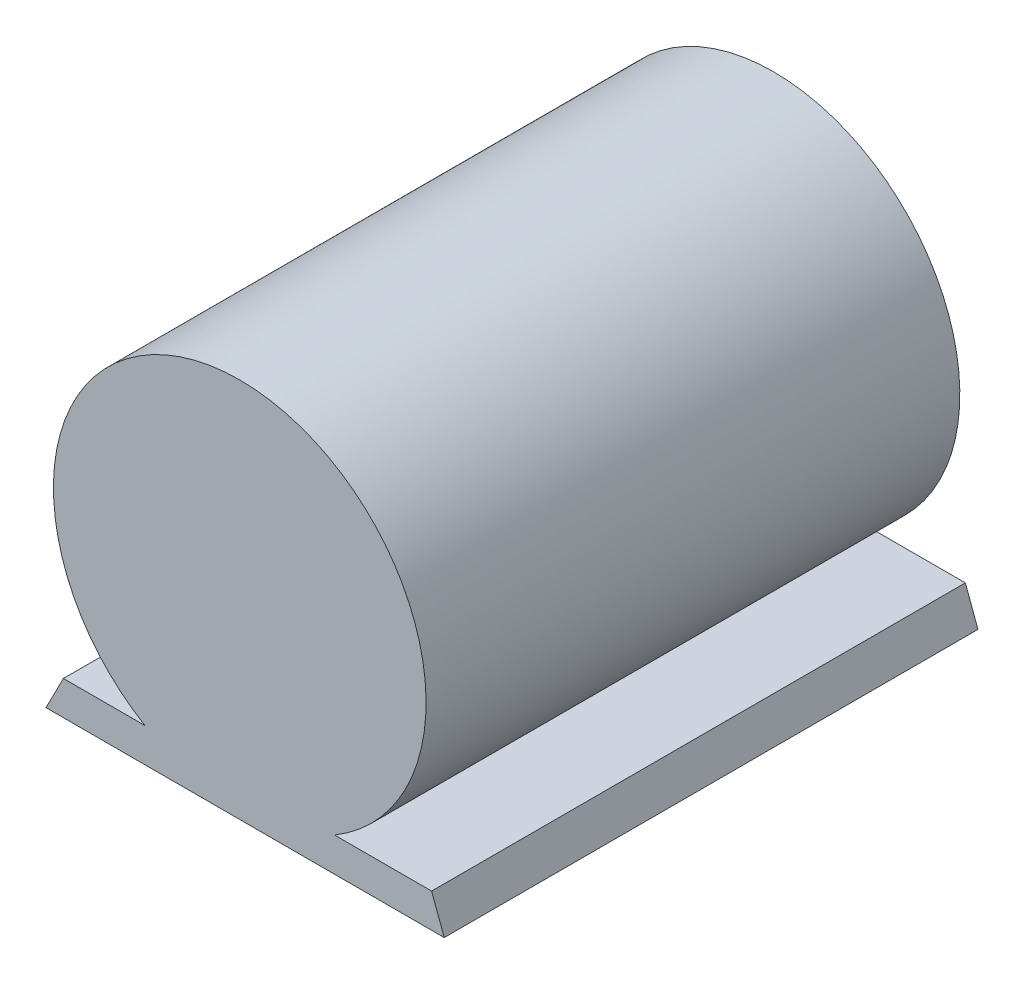
SolidWorks part; units mm, degrees
ref_plane "前视基准面" through (0, 0, 0) normal (0, 0, 1) x (1, 0, 0)
ref_plane "上视基准面" through (0, 0, 0) normal (0, 1, 0) x (1, 0, 0)
ref_plane "右视基准面" through (0, 0, 0) normal (1, 0, 0) x (0, 0, -1)
sketch "草图4" plane through (0, 0, 0) normal (0, 0, 1) x (1, 0, 0)
  line L0 (-63.4448, -57.7095) -> (-34.0779, -57.7095)
  line L1 (69.007, -57.7095) -> (73.5547, -69.9314)
  line L2 (73.5547, -69.9314) -> (-69.6979, -69.9314)
  line L3 (-69.6979, -69.9314) -> (-63.4448, -57.7095)
  line L4 (34.0779, -57.7095) -> (69.007, -57.7095)
  arc A0 (34.0779, -57.7095) -> (-34.0779, -57.7095) centre (0, 0) ccw
extrude "凸台-拉伸2" add sketch "草图4" along normal blind 192 contours L0 A0 | A0 L0 L3 L2 L1 region at (0.2576, -5.2892, 0)
sketch "草图5" plane through (0, 0, 0) normal (0, 0, -1) x (-1, 0, 0)
  circle A0 centre (0, 0) radius 60
extrude "切除-拉伸2" cut sketch "草图5" against normal blind 167
sketch "草图6" plane through (0, 0, 0) normal (0, 0, -1) x (-1, 0, 0)
  circle A0 centre (0, 0) radius 65
extrude "切除-拉伸3" cut sketch "草图6" against normal blind 167
sketch "草图7" plane through (0, 0, 0) normal (0, 0, -1) x (-1, 0, 0)
  line L0 (-50.4249, -41.0162) -> (50.4249, -41.0162)
  arc A0 (-50.4249, -41.0162) -> (50.4249, -41.0162) centre (0, 0) ccw
  arc A1 (-47.8977, -41.0162) -> (47.8977, -41.0162) centre (0, 0) ccw
  circle M1 centre (0, 0) radius 65
extrude "凸台-拉伸3" add sketch "草图7" against normal blind 81 contours A1 L0 M1 region at (49.1613, -42.0529, 0)
sketch "草图8" plane through (0, 0, 0) normal (0, 0, -1) x (-1, 0, 0)
  line L1 (-15.7468, -63.5922) -> (15.9641, -63.5922)
  line L2 (-15.7468, -63.5922) -> (-15.7468, -67.3976)
  line L3 (-15.7468, -67.3976) -> (15.9641, -67.3976)
  line L4 (15.9641, -63.5922) -> (15.9641, -67.3976)
extrude "凸台-拉伸4" add sketch "草图8" along normal blind 7
sketch "草图9" plane through (0, 0, -7) normal (0, 0, -1) x (-1, 0, 0)
  line L1 (-4.8769, -66.7917) -> (4.8769, -66.7917)
  line L2 (-4.8769, -66.7917) -> (-4.8769, -64.8313)
  line L3 (-4.8769, -64.8313) -> (4.8769, -64.8313)
  line L4 (4.8769, -66.7917) -> (4.8769, -64.8313)
  line L5 (-4.8769, -66.7917) -> (4.8769, -64.8313) construction
  line L6 (-4.8769, -64.8313) -> (4.8769, -66.7917) construction
  point P0 (0, -65.8115)
extrude "切除-拉伸4" cut sketch "草图9" against normal blind 3
fillet "圆角1" radius 3 3 edges at (-4.8769, -65.8115, -7) (4.8769, -65.8115, -7) (0, -64.8313, -7)
sketch "草图10" plane through (0, 0, 81) normal (0, 0, 1) x (1, 0, 0)
  line L0 (-49.3548, -43.0551) -> (49.3548, -43.0551)
  arc A0 (-49.3548, -43.0551) -> (49.3548, -43.0551) centre (0, 0) ccw
extrude "凸台-拉伸5" add sketch "草图10" along normal blind 3
